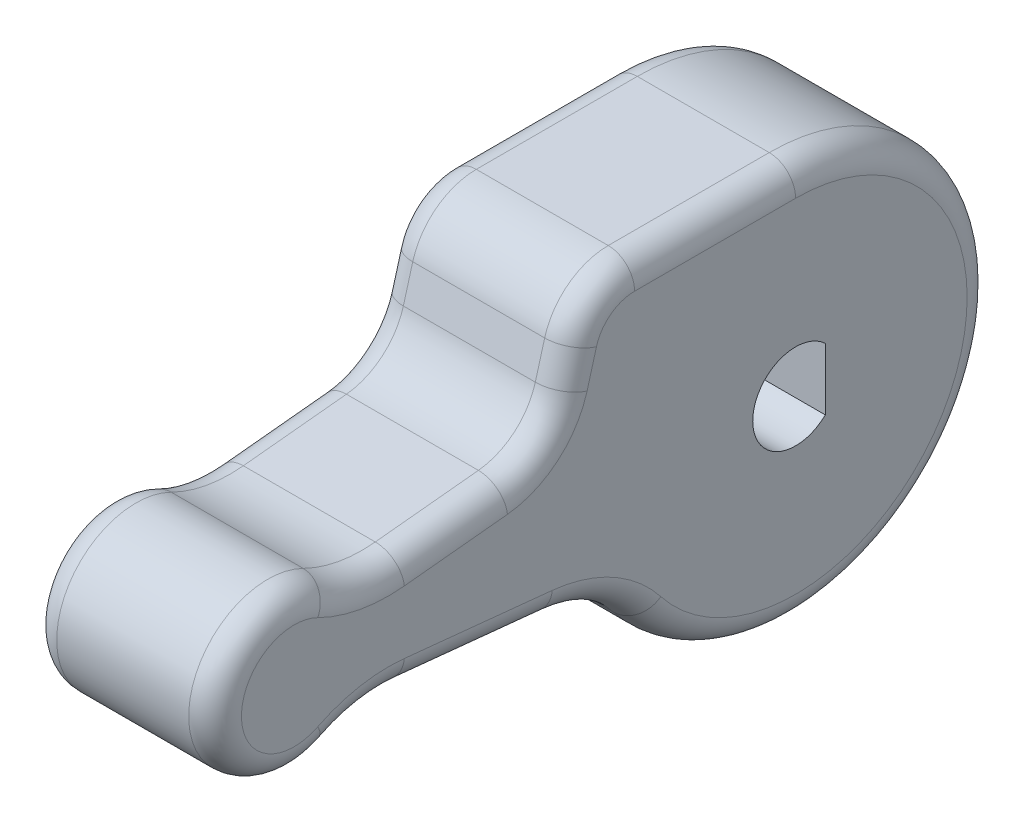
SolidWorks part; units mm, degrees
material "ABS"
ref_plane "Front Plane" through (0, 0, 0) normal (0, 0, 1) x (1, 0, 0)
ref_plane "Top Plane" through (0, 0, 0) normal (0, 1, 0) x (1, 0, 0)
ref_plane "Right Plane" through (0, 0, 0) normal (1, 0, 0) x (0, 0, -1)
sketch "Sketch1" plane through (0, 0, 0) normal (1, 0, 0) x (0, 0, -1)
  line L0 (1.125, -1.1726) -> (1.125, 1.1726)
  line L1 (-22, 0) -> (-19, 0) construction
  line L2 (-19, 0) -> (0, 0) construction
  line L3 (-16.7639, 2) -> (-6.8739, 3)
  line L4 (-16.7639, -2) -> (-6.8739, -3)
  line L5 (0, 0) -> (7.5, 0) construction
  line L6 (-1.625, 0) -> (1.125, 0) construction
  arc A0 (1.125, 1.1726) -> (1.125, -1.1726) centre (0, 0) ccw
  arc A1 (-6.8739, -3) -> (-6.8739, 3) centre (0, 0) ccw
  arc A2 (-16.7639, 2) -> (-16.7639, -2) centre (-19, 0) ccw
  dimension "D1" = 6
  dimension "D2" = 15
  dimension "D4" = 6
  dimension "D6" = 1.625
  dimension "D3" = 22
  dimension "D5" = 4
  dimension "D7" = 2.75
extrude "Boss-Extrude1" add sketch "Sketch1" along normal mid plane 7
fillet "Fillet1" radius 5 4 edges at (0, 2, 16.7639) (0, -3, 6.8739) (0, -2, 16.7639) (0, 3, 6.8739)
ref_plane "Plane1" through (0, 0, -7.625) normal (0, 0, 1) x (1, 0, 0)
hole_wizard "Hole1" positions "Sketch2" profile "Sketch3" legacy
sketch "Sketch2" plane through (0, 0, -7.625) normal (0, 0, 1) x (1, 0, 0)
  point P0 (0, 0)
sketch "Sketch3" plane through (0, 0, -7.625) normal (1, 0, 0) x (0, 1, 0)
  line L0 (0, 0) -> (0, 8)
  line L1 (0, 8) -> (1.25, 8)
  line L2 (1.25, 8) -> (1.25, 3)
  line L3 (1.25, 3) -> (1.75, 3)
  line L4 (1.75, 3) -> (1.75, 0)
  line L5 (1.75, 0) -> (0, 0)
  line L6 (0, 110) -> (0, -10) construction
  dimension "Diameter" = 2.5
  dimension "Depth" = 8
  dimension "C-Bore Diameter" = 3.5
  dimension "C-Bore Depth" = 3
sketch "Sketch4" plane through (3.5, 0, 0) normal (1, 0, 0) x (0, 0, -1)
  line L0 (0, 7.5) -> (-8, 7.5)
  line L1 (-8, 7.5) -> (-9.3226, 2.7524)
  arc A0 (-5.8954, -4.6362) -> (-5.8954, 4.6362) centre (0, 0) ccw construction
  arc A1 (-9.3226, 2.7524) -> (-5.8954, 4.6362) centre (-9.8256, 7.727) ccw construction
  arc A2 (-9.3226, 2.7524) -> (-5.8954, 4.6362) centre (-9.8256, 7.727) ccw
  arc A3 (0, 7.5) -> (-5.8954, 4.6362) centre (0, 0) ccw
  dimension "D1" = 8
extrude "Boss-Extrude2" add sketch "Sketch4" against normal through all
fillet "Fillet3" radius 2.5 2 edges at (0, 2.7524, 9.3226) (0, 7.5, 8)
fillet "Fillet2" radius 1 22 edges at (-3.5, -3.3453, 7.4172) (-3.5, -2.469, 12.1257) (-3.5, -2.2417, 16.3308) (-3.5, 0, 22) (-3.5, 2.2417, 16.3308) (-3.5, 2.3831, 12.975) (3.5, -3.3453, 7.4172) (3.5, -2.469, 12.1257) (3.5, -2.2417, 16.3308) (3.5, 0, 22) (3.5, 2.2417, 16.3308) (3.5, 2.3831, 12.975) (-3.5, -3.2771, -6.7462) (3.5, -3.2771, -6.7462) (-3.5, 7.5, 3.0506) (3.5, 7.5, 3.0506) (-3.5, 3.1558, 9.6623) (-3.5, 5.034, 8.687) (-3.5, 6.9909, 7.6133) (3.5, 3.1558, 9.6623) (3.5, 5.034, 8.687) (3.5, 6.9909, 7.6133)
